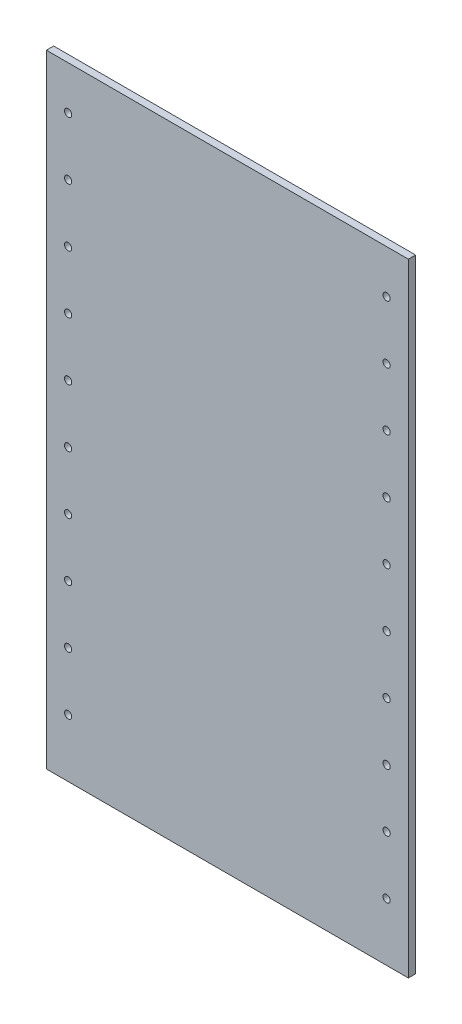
SolidWorks part; units mm, degrees
material "Copper"
ref_plane "Front Plane" through (0, 0, 0) normal (0, 0, 1) x (1, 0, 0)
ref_plane "Top Plane" through (0, 0, 0) normal (0, 1, 0) x (1, 0, 0)
ref_plane "Right Plane" through (0, 0, 0) normal (1, 0, 0) x (0, 0, -1)
sketch "Sketch1" plane through (0, 0, 0) normal (0, 0, 1) x (1, 0, 0)
  line L1 (0, 0) -> (158.76, 0)
  line L2 (0, 0) -> (0, -273.05)
  line L3 (0, -273.05) -> (158.76, -273.05)
  line L4 (158.76, 0) -> (158.76, -273.05)
  circle A0 centre (9.53, -19.05) radius 1.5875
  circle A1 centre (149.23, -19.05) radius 1.5875
  circle A2 centre (149.23, -44.45) radius 1.5875
  circle A3 centre (149.23, -69.85) radius 1.5875
  circle A4 centre (149.23, -95.25) radius 1.5875
  circle A5 centre (149.23, -120.65) radius 1.5875
  circle A6 centre (149.23, -146.05) radius 1.5875
  circle A7 centre (149.23, -171.45) radius 1.5875
  circle A8 centre (149.23, -196.85) radius 1.5875
  circle A9 centre (149.23, -222.25) radius 1.5875
  circle A10 centre (149.23, -247.65) radius 1.5875
  circle A11 centre (9.53, -44.45) radius 1.5875
  circle A12 centre (9.53, -69.85) radius 1.5875
  circle A13 centre (9.53, -95.25) radius 1.5875
  circle A14 centre (9.53, -120.65) radius 1.5875
  circle A15 centre (9.53, -146.05) radius 1.5875
  circle A16 centre (9.53, -171.45) radius 1.5875
  circle A17 centre (9.53, -196.85) radius 1.5875
  circle A18 centre (9.53, -222.25) radius 1.5875
  circle A19 centre (9.53, -247.65) radius 1.5875
  dimension "D3" = 3.175
  dimension "D1" = 158.76
  dimension "D2" = 273.05
  dimension "D4" = 19.05
  dimension "D5" = 9.53
  dimension "D8" = 25.4
  dimension "D9" = 9.53
  dimension "D6" = 2
  dimension "D7" = 10
extrude "Boss-Extrude1" add sketch "Sketch1" along normal blind 3.175
equation "\"D9@Sketch1\"=\"D5@Sketch1\""
